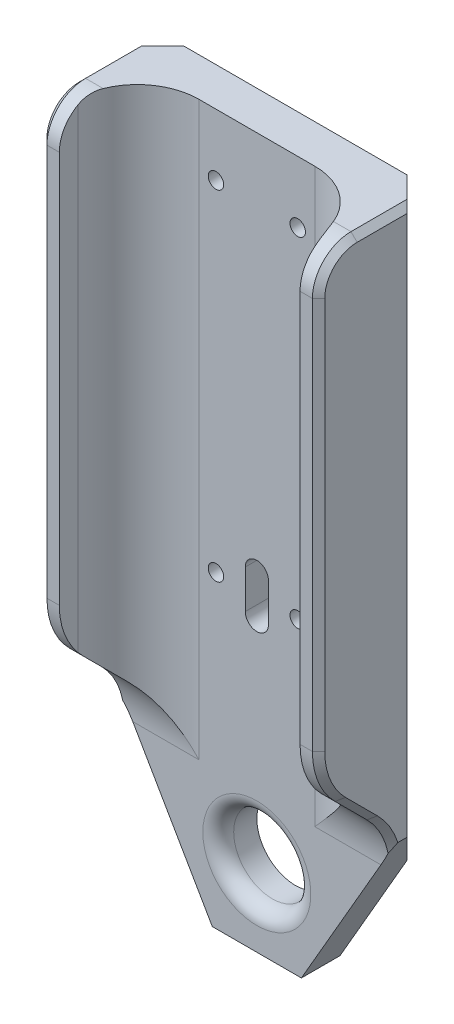
SolidWorks part; units mm, degrees
ref_plane "Front Plane" through (0, 0, 0) normal (0, 0, 1) x (1, 0, 0)
ref_plane "Top Plane" through (0, 0, 0) normal (0, 1, 0) x (1, 0, 0)
ref_plane "Right Plane" through (0, 0, 0) normal (1, 0, 0) x (0, 0, -1)
sketch "Sketch1" plane through (0, 0, 0) normal (0, 1, 0) x (1, 0, 0)
  line L0 (-6.6304, 0) -> (6.6304, 0)
  line L1 (-15.6026, -15) -> (-15.5, -12.651)
  line L2 (-7.5076, -5) -> (7.5076, -5)
  line L3 (15.5, -12.651) -> (15.6026, -15)
  line L4 (0, -1000) -> (0, 49000) construction
  line L5 (-15.6026, -15) -> (-18.0026, -15)
  line L6 (-18.0026, -15) -> (-18.0026, -3.5355)
  line L7 (-18.0026, -3.5355) -> (-14.467, 0)
  line L8 (-14.467, 0) -> (-6.6304, 0)
  line L9 (6.6304, 0) -> (14.467, 0)
  line L10 (14.467, 0) -> (18.0026, -3.5355)
  line L11 (18.0026, -3.5355) -> (18.0026, -15)
  line L12 (18.0026, -15) -> (15.6026, -15)
  arc A0 (-7.5076, -5) -> (-15.5, -12.651) centre (-7.5076, -13) ccw
  arc A1 (7.5076, -5) -> (15.5, -12.651) centre (7.5076, -13) cw
  point P2 (0, 0)
  point P10 (0, -5)
  point P14 (0, 0)
  point P22 (0, 0)
  dimension "D5" = 8
  dimension "D1" = 5
  dimension "D2" = 31
  dimension "D3" = 10
  dimension "D4" = 5
  dimension "D6" = 5
  dimension "D7" = 2.4
extrude "Boss-Extrude1" add sketch "Sketch1" along normal blind 60
extrude "Boss-Extrude2" add sketch "Sketch1<2>" against normal blind 32
sketch "Sketch1<2>" plane through (0, 0, 0) normal (0, 1, 0) x (1, 0, 0) same geometry as "Sketch1"
sketch "Sketch2" plane through (0, 0, 0) normal (1, 0, 0) x (0, 0, -1)
  line L0 (-15, 0) -> (-5, -10)
  line L1 (-5, -10) -> (-5, -32)
  line L2 (-5, -32) -> (-15, -32)
  line L3 (-15, -32) -> (-15, 0)
  point P2 (0, 0)
  point P5 (0, 0)
  point P9 (0, 0)
  point P13 (0, 0)
  dimension "D1" = 45
extrude "Cut-Extrude1" cut sketch "Sketch2" against normal through all both and the other way through all
sketch "Sketch3" plane through (0, 0, 5) normal (0, 0, 1) x (1, 0, 0)
  line L4 (18.0026, -10.8187) -> (18.0026, -32)
  line L5 (18.0026, -32) -> (5.7735, -32)
  line L6 (5.7735, -32) -> (18.0026, -10.8187)
  line L7 (4.3301, -24.5) -> (8.6603, -27) construction
  line L9 (0, -27) -> (0, -32) construction
  line L10 (0, -1040) -> (0, 48960) construction
  line L11 (-18.0026, -32) -> (-5.7735, -32)
  line L12 (-18.0026, -10.8187) -> (-18.0026, -32)
  line L13 (-5.7735, -32) -> (-18.0026, -10.8187)
  circle A0 centre (0, -22) radius 5
  point P2 (0, 0)
  point P4 (0, -27)
  point P5 (18.2526, -22.8324)
  point P12 (4.3301, -24.5)
  point P19 (16.5214, -48.8094)
  point P20 (0, 0)
  point P22 (0, 0)
  point P24 (0, -31.0856)
  point P25 (8.1608, -30.2883)
  dimension "D1" = 10
  dimension "D2" = 5
  dimension "D3" = 30
extrude "Cut-Extrude2" cut sketch "Sketch3" against normal through all
chamfer "Chamfer1" [suppressed] distance 1 angle 45
fillet "Fillet1" radius 2 1 edges at (5, -22, 5)
sketch "Sketch4" plane through (0, 0, 0) normal (0, 0, 1) x (1, 0, 0)
  line L0 (0, 52) -> (0, 60) construction
  line L1 (-5.3, 8) -> (5.3, 8) construction
  line L2 (-5.3, 8) -> (-5.3, 52) construction
  line L3 (-5.3, 52) -> (5.3, 52) construction
  line L4 (5.3, 8) -> (5.3, 52) construction
  line L5 (0, 52) -> (0, 8) construction
  line L6 (-5.3, 30) -> (5.3, 30) construction
  line L7 (0, 8) -> (0, 0) construction
  line L8 (-7.5076, 0) -> (7.5076, 0) construction
  line L9 (-7.5076, 60) -> (7.5076, 60) construction
  circle A0 centre (5.3, 52) radius 1
  circle A1 centre (-5.3, 52) radius 1
  circle A2 centre (-5.3, 8) radius 1
  circle A3 centre (5.3, 8) radius 1
  point P0 (0, 30)
  dimension "D3" = 2
  dimension "D1" = 10.6
  dimension "D2" = 8
extrude "Cut-Extrude6" cut sketch "Sketch4" against normal through all and the other way through all
sketch "Sketch5" plane through (0, 0, 0) normal (0, 0, 1) x (1, 0, 0)
  line L0 (0, 5.5) -> (0, 10.5) construction
  line L1 (-1.5, 5.5) -> (-1.5, 10.5)
  line L2 (1.5, 5.5) -> (1.5, 10.5)
  line L3 (-7.5076, 0) -> (7.5076, 0) construction
  arc A0 (-1.5, 5.5) -> (1.5, 5.5) centre (0, 5.5) ccw
  arc A1 (1.5, 10.5) -> (-1.5, 10.5) centre (0, 10.5) ccw
  point P2 (0, 8)
  point P8 (0, 0)
  point P9 (0, 0)
  dimension "D1" = 3
  dimension "D2" = 5
  dimension "D3" = 8
extrude "Cut-Extrude7" cut sketch "Sketch5" along normal through all
fillet "Fillet2" radius 5 2 edges at (16.8026, 60, 15) (-16.8026, 60, 15)
fillet "Fillet3" radius 10 2 edges at (-16.8026, 0, 15) (16.8026, 0, 15)
fillet "Fillet4" radius 10 2 edges at (-12.7551, -10, 5) (12.7551, -10, 5)
chamfer "Chamfer2" distance 0.8 angle 45 12 edges at (18.0026, -8.8125, 6.5386) (18.0026, 60, 6.7678) (18.0026, -5, 10) (18.0026, 58.5355, 13.5355) (18.0026, 0.3153, 14.2388) (18.0026, 29.5711, 15) (-18.0026, -8.8125, 6.5386) (-18.0026, 60, 6.7678) (-18.0026, -5, 10) (-18.0026, 58.5355, 13.5355) (-18.0026, 0.3153, 14.2388) (-18.0026, 29.5711, 15)
